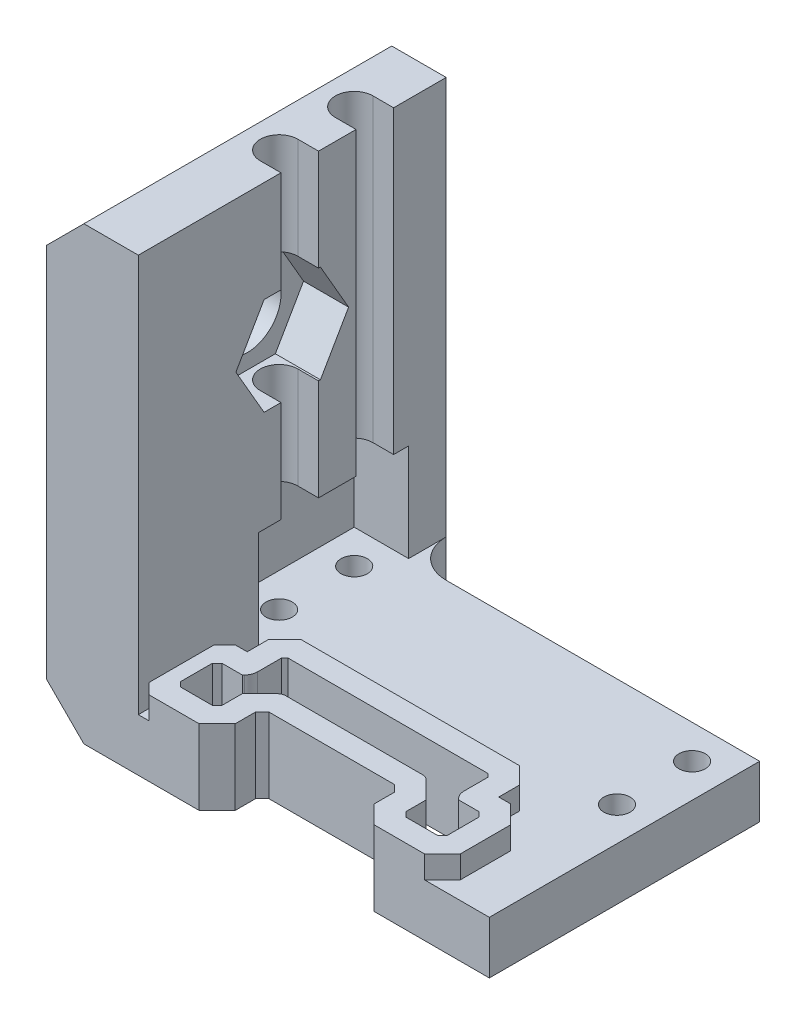
SolidWorks part; units mm, degrees
ref_plane "Front Plane" through (0, 0, 0) normal (0, 0, 1) x (1, 0, 0)
ref_plane "Top Plane" through (0, 0, 0) normal (0, 1, 0) x (1, 0, 0)
ref_plane "Right Plane" through (0, 0, 0) normal (1, 0, 0) x (0, 0, -1)
ref_plane "Plane1" through (0, 200, 0) normal (0, 1, 0) x (1, 0, 0)
sketch "Sketch1" plane through (0, 200, 0) normal (0, 1, 0) x (1, 0, 0)
  line L0 (0, -3.8557) -> (0.25, -4)
  line L1 (0.25, -4) -> (9.0787, -4)
  line L2 (10.1394, -4.4394) -> (12.5, -6.8)
  line L3 (12.5, -6.8) -> (12.5, -9.5)
  line L4 (12.5, -9.5) -> (13, -10)
  line L5 (13, -10) -> (17, -10)
  line L6 (17, -10) -> (17.5, -9.5)
  line L7 (17.5, -9.5) -> (17.5, -5.5)
  line L8 (17.5, -5.5) -> (17, -5)
  line L9 (17, -5) -> (14.3, -5)
  line L10 (14.3, -5) -> (14.0858, -4.7858)
  line L11 (13.5, -3.3716) -> (13.5, -0.3)
  line L12 (13.5, -0.3) -> (13.2, 0)
  line L13 (13.2, 0) -> (7.5, 0)
  line L14 (7.5, 0) -> (7.4, -0.1)
  line L15 (7.4, -0.1) -> (-7.4, -0.1)
  line L16 (-7.4, -0.1) -> (-7.5, 0)
  line L17 (-7.5, 0) -> (-13.2, 0)
  line L18 (-13.2, 0) -> (-13.5, -0.3)
  line L19 (-13.5, -0.3) -> (-13.5, -3.3716)
  line L20 (-14.0858, -4.7858) -> (-14.3, -5)
  line L21 (-14.3, -5) -> (-17, -5)
  line L22 (-17, -5) -> (-17.5, -5.5)
  line L23 (-17.5, -5.5) -> (-17.5, -9.5)
  line L24 (-17.5, -9.5) -> (-17, -10)
  line L25 (-17, -10) -> (-13, -10)
  line L26 (-13, -10) -> (-12.5, -9.5)
  line L27 (-12.5, -9.5) -> (-12.5, -6.8)
  line L28 (-12.5, -6.8) -> (-10.1394, -4.4394)
  line L29 (-9.0787, -4) -> (-0.25, -4)
  line L30 (-0.25, -4) -> (0, -3.8557)
  arc A0 (9.0787, -4) -> (10.1394, -4.4394) centre (9.0787, -5.5) cw
  arc A1 (14.0858, -4.7858) -> (13.5, -3.3716) centre (15.5, -3.3716) cw
  arc A2 (-13.5, -3.3716) -> (-14.0858, -4.7858) centre (-15.5, -3.3716) cw
  arc A3 (-10.1394, -4.4394) -> (-9.0787, -4) centre (-9.0787, -5.5) cw
extrude "Boss-Extrude1" add sketch "Sketch1" against normal blind 400
ref_plane "Plane2" through (0, 210, 0) normal (0, 1, 0) x (1, 0, 0)
sketch "Sketch2" plane through (0, 210, 0) normal (0, 1, 0) x (1, 0, 0)
  line L0 (-8.3538, -7.25) -> (8.3538, -7.25)
  line L1 (8.3538, -7.25) -> (9.25, -8.1462)
  line L2 (13.3036, 0.25) -> (-13.3036, 0.25)
  line L3 (-13.3036, 0.25) -> (-13.75, -0.1965)
  line L4 (-13.75, -0.1965) -> (-13.75, -3.3716)
  line L5 (-14.2626, -4.609) -> (-14.4036, -4.75)
  line L6 (-14.4036, -4.75) -> (-17.1036, -4.75)
  line L7 (-17.1036, -4.75) -> (-17.75, -5.3965)
  line L8 (-17.75, -5.3965) -> (-17.75, -9.6036)
  line L9 (-17.75, -9.6036) -> (-17.1036, -10.25)
  line L10 (-17.1036, -10.25) -> (-12.8965, -10.25)
  line L11 (-12.8965, -10.25) -> (-12.25, -9.6036)
  line L12 (-12.25, -9.6036) -> (-12.25, -6.9036)
  line L13 (-12.25, -6.9036) -> (-9.9626, -4.6162)
  line L14 (-9.0787, -4.25) -> (9.0787, -4.25)
  line L15 (9.9626, -4.6162) -> (12.25, -6.9036)
  line L16 (12.25, -6.9036) -> (12.25, -9.6036)
  line L17 (12.25, -9.6036) -> (12.8965, -10.25)
  line L18 (12.8965, -10.25) -> (17.1036, -10.25)
  line L19 (17.1036, -10.25) -> (17.75, -9.6036)
  line L20 (17.75, -9.6036) -> (17.75, -5.3965)
  line L21 (17.75, -5.3965) -> (17.1036, -4.75)
  line L22 (17.1036, -4.75) -> (14.4036, -4.75)
  line L23 (14.4036, -4.75) -> (14.2626, -4.609)
  line L24 (13.75, -3.3716) -> (13.75, -0.1965)
  line L25 (13.75, -0.1965) -> (13.3036, 0.25)
  line L26 (9.25, -8.1462) -> (9.25, -10.8462)
  line L27 (9.25, -10.8462) -> (11.6538, -13.25)
  line L28 (11.6538, -13.25) -> (18.3462, -13.25)
  line L29 (18.3462, -13.25) -> (20.75, -10.8462)
  line L30 (20.75, -10.8462) -> (20.75, -4.1538)
  line L31 (20.75, -4.1538) -> (18.3462, -1.75)
  line L32 (18.3462, -1.75) -> (16.75, -1.75)
  line L33 (16.75, -1.75) -> (16.75, -1.75)
  line L34 (16.75, -1.75) -> (16.75, 1.0462)
  line L35 (16.75, 1.0462) -> (14.5462, 3.25)
  line L36 (14.5462, 3.25) -> (-14.5462, 3.25)
  line L37 (-14.5462, 3.25) -> (-16.75, 1.0462)
  line L38 (-16.75, 1.0462) -> (-16.75, -1.75)
  line L39 (-16.75, -1.75) -> (-16.75, -1.75)
  line L40 (-16.75, -1.75) -> (-18.3462, -1.75)
  line L41 (-18.3462, -1.75) -> (-20.75, -4.1538)
  line L42 (-20.75, -4.1538) -> (-20.75, -10.8462)
  line L43 (-20.75, -10.8462) -> (-18.3462, -13.25)
  line L44 (-18.3462, -13.25) -> (-11.6538, -13.25)
  line L45 (-11.6538, -13.25) -> (-9.25, -10.8462)
  line L46 (-9.25, -10.8462) -> (-9.25, -8.1462)
  line L47 (-9.25, -8.1462) -> (-8.3538, -7.25)
  arc A0 (-14.2626, -4.609) -> (-13.75, -3.3716) centre (-15.5, -3.3716) ccw
  arc A1 (-9.0787, -4.25) -> (-9.9626, -4.6162) centre (-9.0787, -5.5) ccw
  arc A2 (9.9626, -4.6162) -> (9.0787, -4.25) centre (9.0787, -5.5) ccw
  arc A3 (13.75, -3.3716) -> (14.2626, -4.609) centre (15.5, -3.3716) ccw
  arc A4 (8.3538, -7.25) -> (8.3538, -7.25) centre (8.3538, -7.25) ccw
  arc A5 (16.75, -1.75) -> (16.75, -1.75) centre (16.75, -1.75) ccw
  arc A6 (-16.75, -1.75) -> (-16.75, -1.75) centre (-16.75, -1.75) ccw
  arc A7 (-8.3538, -7.25) -> (-8.3538, -7.25) centre (-8.3538, -7.25) ccw
  dimension "D1" = 3
extrude "Boss-Extrude2" add sketch "Sketch2" along normal blind 10 separate body
sketch "Sketch3" plane through (0, 200, 0) normal (0, 1, 0) x (1, 0, 0)
  line L0 (7.4, -0.1) -> (-7.4, -0.1) construction
  circle A0 centre (0, -0.1) radius 43.001
extrude "Cut-Extrude1" cut sketch "Sketch3" against normal blind 447.3602
sketch "Sketch4" plane through (0, 210, 0) normal (0, -1, 0) x (-1, 0, 0)
  line L0 (-13.3036, 0.25) -> (13.3036, 0.25) construction
  line L1 (27, 22.75) -> (-27, 22.75)
  line L2 (27, 22.75) -> (27, -13.25)
  line L3 (27, -13.25) -> (18.3462, -13.25)
  line L4 (-27, 22.75) -> (-27, -13.25)
  line L5 (-27, -13.25) -> (-18.3462, -13.25)
  line L25 (8.3538, -7.25) -> (9.25, -8.1462)
  line L26 (9.25, -8.1462) -> (9.25, -10.8462)
  line L27 (9.25, -10.8462) -> (11.6538, -13.25)
  line L28 (11.6538, -13.25) -> (18.3462, -13.25)
  line L29 (18.3462, -13.25) -> (20.75, -10.8462)
  line L30 (20.75, -10.8462) -> (20.75, -4.1538)
  line L31 (20.75, -4.1538) -> (18.3462, -1.75)
  line L32 (18.3462, -1.75) -> (16.75, -1.75)
  line L33 (16.75, -1.75) -> (16.75, 1.0462)
  line L34 (16.75, 1.0462) -> (14.5462, 3.25)
  line L35 (14.5462, 3.25) -> (-14.5462, 3.25)
  line L36 (-14.5462, 3.25) -> (-16.75, 1.0462)
  line L37 (-16.75, 1.0462) -> (-16.75, -1.75)
  line L38 (-16.75, -1.75) -> (-18.3462, -1.75)
  line L39 (-18.3462, -1.75) -> (-20.75, -4.1538)
  line L40 (-20.75, -4.1538) -> (-20.75, -10.8462)
  line L41 (-20.75, -10.8462) -> (-18.3462, -13.25)
  line L42 (-18.3462, -13.25) -> (-11.6538, -13.25)
  line L43 (-11.6538, -13.25) -> (-9.25, -10.8462)
  line L44 (-9.25, -10.8462) -> (-9.25, -8.1462)
  line L45 (-9.25, -8.1462) -> (-8.3538, -7.25)
  line L46 (-8.3538, -7.25) -> (8.3538, -7.25)
  line L47 (8.3538, -7.25) -> (9.25, -8.1462)
  line L48 (9.25, -8.1462) -> (9.25, -10.8462)
  line L49 (9.25, -10.8462) -> (11.6538, -13.25)
  line L50 (11.6538, -13.25) -> (18.3462, -13.25)
  line L51 (18.3462, -13.25) -> (20.75, -10.8462)
  line L52 (20.75, -10.8462) -> (20.75, -4.1538)
  line L53 (20.75, -4.1538) -> (18.3462, -1.75)
  line L54 (18.3462, -1.75) -> (16.75, -1.75)
  line L55 (16.75, -1.75) -> (16.75, 1.0462)
  line L56 (16.75, 1.0462) -> (14.5462, 3.25)
  line L57 (14.5462, 3.25) -> (-14.5462, 3.25)
  line L58 (-14.5462, 3.25) -> (-16.75, 1.0462)
  line L59 (-16.75, 1.0462) -> (-16.75, -1.75)
  line L60 (-16.75, -1.75) -> (-18.3462, -1.75)
  line L61 (-18.3462, -1.75) -> (-20.75, -4.1538)
  line L62 (-20.75, -4.1538) -> (-20.75, -10.8462)
  line L63 (-20.75, -10.8462) -> (-18.3462, -13.25)
  line L64 (-18.3462, -13.25) -> (-11.6538, -13.25)
  line L65 (-11.6538, -13.25) -> (-9.25, -10.8462)
  line L66 (-9.25, -10.8462) -> (-9.25, -8.1462)
  line L67 (-9.25, -8.1462) -> (-8.3538, -7.25)
  line L68 (-8.3538, -7.25) -> (8.3538, -7.25)
  point P8 (0, 22.75)
  point P29 (0, 0.25)
  line M32 (20.75, -4.1538) -> (18.3462, -1.75)
  line M33 (18.3462, -1.75) -> (16.75, -1.75)
  line M34 (16.75, -1.75) -> (16.75, 1.0462)
  line M35 (16.75, 1.0462) -> (14.5462, 3.25)
  line M36 (14.5462, 3.25) -> (-14.5462, 3.25)
  line M37 (-14.5462, 3.25) -> (-16.75, 1.0462)
  line M38 (-16.75, 1.0462) -> (-16.75, -1.75)
  line M39 (-16.75, -1.75) -> (-18.3462, -1.75)
  line M40 (-18.3462, -1.75) -> (-20.75, -4.1538)
  dimension "D2" = 19.5
  dimension "D3" = 54
  dimension "D4" = 0
  dimension "D1" = 0
extrude "Boss-Extrude3" add sketch "Sketch4" against normal blind 7 contours L1 M40 M39 M38 M37 M36 M35 M34 M33 M32 region at (0, 210, -9.587)
sketch "Sketch5" plane through (0, 210, 0) normal (0, -1, 0) x (-1, 0, 0)
  line L0 (0, 22.75) -> (0, 9.6848) construction
  line L1 (27, 22.75) -> (-27, 22.75) construction
  line L2 (27, 22.75) -> (27, -13.25) construction
  circle A0 centre (22.5, 18.25) radius 1.75
  circle A1 centre (22.5, 8.25) radius 1.75
  circle A2 centre (-22.5, 8.25) radius 1.75
  circle A3 centre (-22.5, 18.25) radius 1.75
  dimension "D4" = 3.5
  dimension "D1" = 10
  dimension "D2" = 4.5
  dimension "D3" = 4.5
extrude "Cut-Extrude2" cut sketch "Sketch5" against normal blind 33
sketch "Sketch6" plane through (-27, 0, 0) normal (-1, 0, 0) x (0, 0, 1)
  line L1 (-22.75, 210) -> (13.25, 210)
  line L2 (-22.75, 210) -> (-22.75, 270)
  line L3 (-22.75, 270) -> (13.25, 270)
  line L4 (13.25, 210) -> (13.25, 270)
  dimension "D1" = 60
extrude "Boss-Extrude4" add sketch "Sketch6" along normal blind 5
sketch "Sketch7" plane through (0, 217, 0) normal (0, 1, 0) x (1, 0, 0)
  line L0 (-20.75, -10.8462) -> (-20.75, -4.1538) construction
  line L1 (-27, -13.25) -> (-19.75, -13.25)
  line L2 (-27, -13.25) -> (-27, 2.75)
  line L3 (-27, 2.75) -> (-19.75, 2.75)
  line L4 (-19.75, -13.25) -> (-19.75, 2.75)
  dimension "D1" = 1
  dimension "D2" = 16
extrude "Boss-Extrude5" add sketch "Sketch7" along normal up to surface (53 mm away) up to face at (-29.5, 270, -4.75)
sketch "Sketch8" plane through (0, 0, -22.75) normal (0, 0, -1) x (-1, 0, 0)
  line L0 (32, 210) -> (-27, 210) construction
  line L1 (32, 270) -> (19.75, 270)
  line L2 (32, 270) -> (32, 210)
  line L3 (32, 210) -> (19.75, 210)
  line L4 (19.75, 270) -> (19.75, 210)
  dimension "D1" = 0
extrude "Boss-Extrude6" add sketch "Sketch8" along normal blind 5
fillet "Fillet1" radius 5 1 edges at (-19.75, 213.5, -22.75)
sketch "Sketch10" plane through (-27, 0, 0) normal (1, 0, 0) x (0, 0, -1)
  line L0 (22.75, 270) -> (22.75, 217) construction
  line L1 (2.75, 270) -> (22.75, 270)
  line L2 (2.75, 270) -> (2.75, 230)
  line L3 (2.75, 230) -> (22.75, 230)
  line L4 (22.75, 270) -> (22.75, 230)
  dimension "D1" = 40
extrude "Boss-Extrude7" add sketch "Sketch10" along normal up to surface (7.25 mm away) up to face at (-19.75, 231, 6.375)
sketch "Sketch9" plane through (-19.75, 0, 0) normal (1, 0, 0) x (0, 0, -1)
  line L0 (-13.25, 250) -> (27.75, 250) construction
  line L1 (14.7555, 250) -> (11.0027, 256.5)
  line L2 (11.0027, 256.5) -> (3.4972, 256.5)
  line L3 (3.4972, 256.5) -> (-0.2556, 250)
  line L4 (-0.2556, 250) -> (3.4972, 243.5)
  line L5 (3.4972, 243.5) -> (11.0027, 243.5)
  line L6 (11.0027, 243.5) -> (14.7555, 250)
  line L8 (-13.25, 270) -> (-13.25, 217) construction
  line L9 (27.75, 270) -> (27.75, 217) construction
  line L10 (27.75, 270) -> (-13.25, 270) construction
  circle A0 centre (7.25, 250) radius 6.5 construction
  point P16 (7.25, 250)
  dimension "D1" = 13
  dimension "D2" = 20
extrude "Cut-Extrude3" cut sketch "Sketch9" against normal blind 6
sketch "Sketch11" plane through (0, 217, 0) normal (0, 1, 0) x (1, 0, 0)
  line L0 (-22.5, 20.75) -> (-17.8248, 20.75)
  line L1 (-17.8248, 20.75) -> (-17.8248, 15.75)
  line L2 (-17.8248, 15.75) -> (-22.5, 15.75)
  line L3 (-22.5, 10.75) -> (-17.8248, 10.75)
  line L4 (-17.8248, 10.75) -> (-17.8248, 5.75)
  line L5 (-17.8248, 5.75) -> (-22.5, 5.75)
  arc A0 (-22.5, 20.75) -> (-22.5, 15.75) centre (-22.5, 18.25) ccw
  arc A1 (-22.5, 10.75) -> (-22.5, 5.75) centre (-22.5, 8.25) ccw
  dimension "D1" = 5
  dimension "D2" = 5
extrude "Cut-Extrude4" cut sketch "Sketch11" along normal through all
sketch "Sketch12" plane through (-25.75, 0, 0) normal (1, 0, 0) x (0, 0, -1)
  line L0 (14.7555, 250) -> (-0.2556, 250) construction
  circle A0 centre (7.25, 250) radius 4.5
  dimension "D1" = 9
extrude "Cut-Extrude5" cut sketch "Sketch12" against normal blind 16
chamfer "Chamfer2" distance 5 angle 45 1 edges at (-32, 270, -7.25)
chamfer "Chamfer3" distance 5 angle 45 1 edges at (-32, 210, -7.25)
sketch "Sketch13" plane through (-32, 0, 0) normal (-1, 0, 0) x (0, 0, 1)
  circle A0 centre (-7.25, 250) radius 4.5
  circle A1 centre (-7.25, 250) radius 6.5
  dimension "D1" = 2
extrude "Boss-Extrude8" add sketch "Sketch13" along normal blind 1
fillet "Fillet2" radius 1 1 edges at (-32, 250, -13.75)
